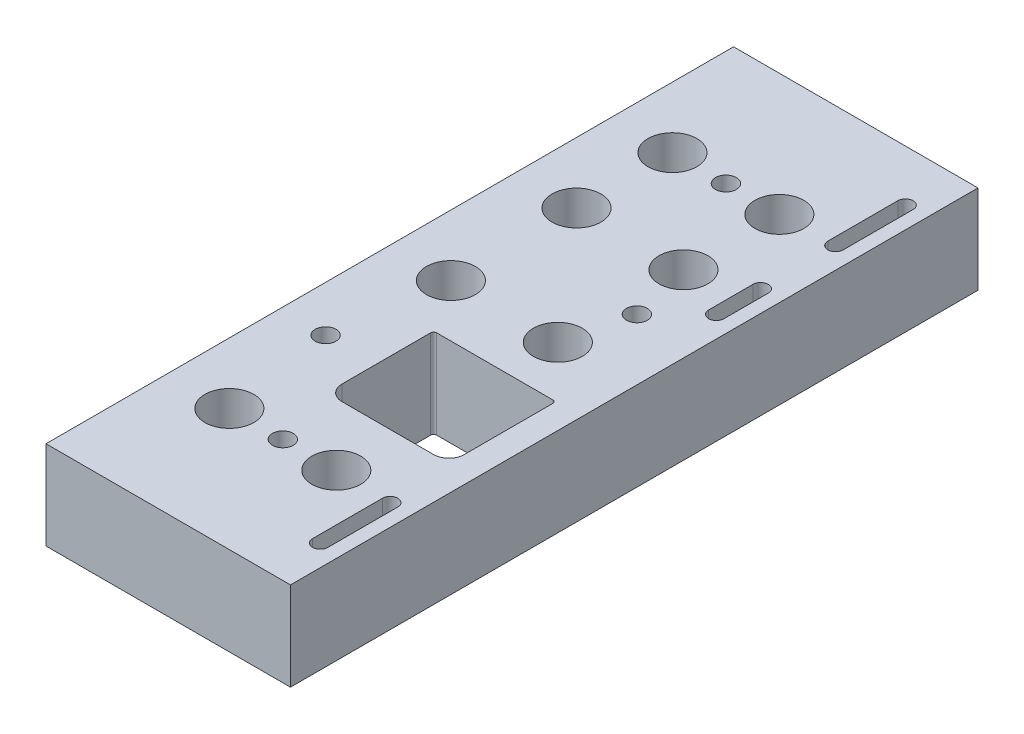
SolidWorks part; units mm, degrees
material "Plain Carbon Steel"
ref_plane "Front Plane" through (0, 0, 0) normal (0, 0, 1) x (1, 0, 0)
ref_plane "Top Plane" through (0, 0, 0) normal (0, 1, 0) x (1, 0, 0)
ref_plane "Right Plane" through (0, 0, 0) normal (1, 0, 0) x (0, 0, -1)
sketch "Sketch1" plane through (0, 0, 0) normal (0, 1, 0) x (1, 0, 0)
  line L1 (-40, -112.5) -> (40, -112.5)
  line L2 (-40, -112.5) -> (-40, 112.5)
  line L3 (-40, 112.5) -> (40, 112.5)
  line L4 (40, -112.5) -> (40, 112.5)
  line L5 (-40, -112.5) -> (40, 112.5) construction
  line L6 (-40, 112.5) -> (40, -112.5) construction
  point P0 (0, 0)
  dimension "D1" = 225
  dimension "D2" = 80
extrude "Boss-Extrude1" add sketch "Sketch1" against normal blind 29
sketch "Sketch2" plane through (0, 0, 0) normal (0, 1, 0) x (1, 0, 0)
  line L0 (30.5, 72.87) -> (30.5, 95.77) construction
  line L1 (35.5, 95.77) -> (35.5, 72.87) construction
  line L2 (30.5, 33.86) -> (30.5, 48.36) construction
  line L3 (35.5, 48.36) -> (35.5, 33.86) construction
  line L4 (31.5, -47.14) -> (31.5, -18.14) construction
  line L5 (30.5, -17.14) -> (-7.5, -17.14) construction
  line L6 (-8.5, -18.14) -> (-8.5, -47.14) construction
  line L7 (-3.5, -52.14) -> (26.5, -52.14) construction
  line L8 (30.5, -95.77) -> (30.5, -72.87) construction
  line L9 (35.5, -72.87) -> (35.5, -95.77) construction
  line L10 (30.5, 72.87) -> (30.5, 95.77)
  line L11 (35.5, 95.77) -> (35.5, 72.87)
  line L12 (30.5, 33.86) -> (30.5, 48.36)
  line L13 (35.5, 48.36) -> (35.5, 33.86)
  line L14 (31.5, -47.14) -> (31.5, -18.14)
  line L15 (30.5, -17.14) -> (-7.5, -17.14)
  line L16 (-8.5, -18.14) -> (-8.5, -47.14)
  line L17 (-3.5, -52.14) -> (26.5, -52.14)
  line L18 (30.5, -95.77) -> (30.5, -72.87)
  line L19 (35.5, -72.87) -> (35.5, -95.77)
  arc A0 (30.5, 72.87) -> (35.5, 72.87) centre (33, 72.87) ccw construction
  arc A1 (35.5, 95.77) -> (30.5, 95.77) centre (33, 95.77) ccw construction
  arc A2 (30.5, 33.86) -> (35.5, 33.86) centre (33, 33.86) ccw construction
  arc A3 (35.5, 48.36) -> (30.5, 48.36) centre (33, 48.36) ccw construction
  arc A4 (26.5, -52.14) -> (31.5, -47.14) centre (26.5, -47.14) ccw construction
  arc A5 (31.5, -18.14) -> (30.5, -17.14) centre (30.5, -18.14) ccw construction
  arc A6 (-7.5, -17.14) -> (-8.5, -18.14) centre (-7.5, -18.14) ccw construction
  arc A7 (-8.5, -47.14) -> (-3.5, -52.14) centre (-3.5, -47.14) ccw construction
  arc A8 (35.5, -72.87) -> (30.5, -72.87) centre (33, -72.87) ccw construction
  arc A9 (30.5, -95.77) -> (35.5, -95.77) centre (33, -95.77) ccw construction
  arc A10 (30.5, 72.87) -> (35.5, 72.87) centre (33, 72.87) ccw
  arc A11 (35.5, 95.77) -> (30.5, 95.77) centre (33, 95.77) ccw
  arc A12 (30.5, 33.86) -> (35.5, 33.86) centre (33, 33.86) ccw
  arc A13 (35.5, 48.36) -> (30.5, 48.36) centre (33, 48.36) ccw
  arc A14 (26.5, -52.14) -> (31.5, -47.14) centre (26.5, -47.14) ccw
  arc A15 (31.5, -18.14) -> (30.5, -17.14) centre (30.5, -18.14) ccw
  arc A16 (-7.5, -17.14) -> (-8.5, -18.14) centre (-7.5, -18.14) ccw
  arc A17 (-8.5, -47.14) -> (-3.5, -52.14) centre (-3.5, -47.14) ccw
  arc A18 (35.5, -72.87) -> (30.5, -72.87) centre (33, -72.87) ccw
  arc A19 (30.5, -95.77) -> (35.5, -95.77) centre (33, -95.77) ccw
extrude "Cut-Extrude1" cut sketch "Sketch2" against normal up to next
sketch "Sketch3" plane through (0, 0, 0) normal (0, 1, 0) x (1, 0, 0)
  line L0 (-40, -112.5) -> (40, -112.5) construction
  line L2 (-40, 112.5) -> (-40, -112.5) construction
  line L3 (30.5, 41.11) -> (-40, 41.11) construction
  line L4 (30.5, 48.36) -> (30.5, 33.86) construction
  line L5 (40, 112.5) -> (-40, 112.5) construction
  line L7 (40, -112.5) -> (40, 112.5) construction
  circle A0 centre (15, 72.5) radius 8
  circle A1 centre (15, 41.11) radius 8
  circle A2 centre (15, 0) radius 8
  circle A3 centre (15, -72.5) radius 8
  circle A4 centre (-20, -72.5) radius 8
  circle A5 centre (-20, 0) radius 8
  circle A6 centre (-20, 41.11) radius 8
  circle A7 centre (-20, 72.5) radius 8
  dimension "D1" = 16
  dimension "D2" = 25
  dimension "D3" = 20
  dimension "D4" = 40
  dimension "D5" = 40
extrude "Cut-Extrude2" cut sketch "Sketch3" against normal blind 20
hole_wizard "M8 Tapped Hole1" positions "Sketch14" profile "Sketch10" tap size "M8" standard "ISO"
sketch "Sketch14" plane through (0, 0, 0) normal (0, 1, 0) x (1, 0, 0)
  line L0 (-20, 72.5) -> (15, 72.5) construction
  line L2 (-20, -72.5) -> (15, -72.5) construction
  point P0 (-25, -36)
  point P2 (20, 20.8639)
  point P4 (-2.5, 72.5)
  point P6 (-2.5, -72.5)
  point P27 (0, 0)
  dimension "D2" = 25
  dimension "D3" = 20
  dimension "D7" = 36
sketch "Sketch10" plane through (-25, 0, 36) normal (1, 0, 0) x (0, 0, 1)
  line L0 (0, 0) -> (0, 21.7929)
  line L1 (0, 21.7929) -> (3.4, 19.75)
  line L2 (3.4, 19.75) -> (3.4, 0)
  line L5 (3.4, 0) -> (0, 0)
  line L10 (0, 21.7929) -> (-3.4, 19.75) construction
  line L11 (0, -6.35) -> (0, 107.95) construction
  dimension "Tap Drill Dia." = 6.8
  dimension "Tap Drill Depth" = 19.75
  dimension "Drill Angle" = 118
cosmetic thread "Hole Thread5"
cosmetic thread "Hole Thread6"
cosmetic thread "Hole Thread7"
cosmetic thread "Hole Thread8"
